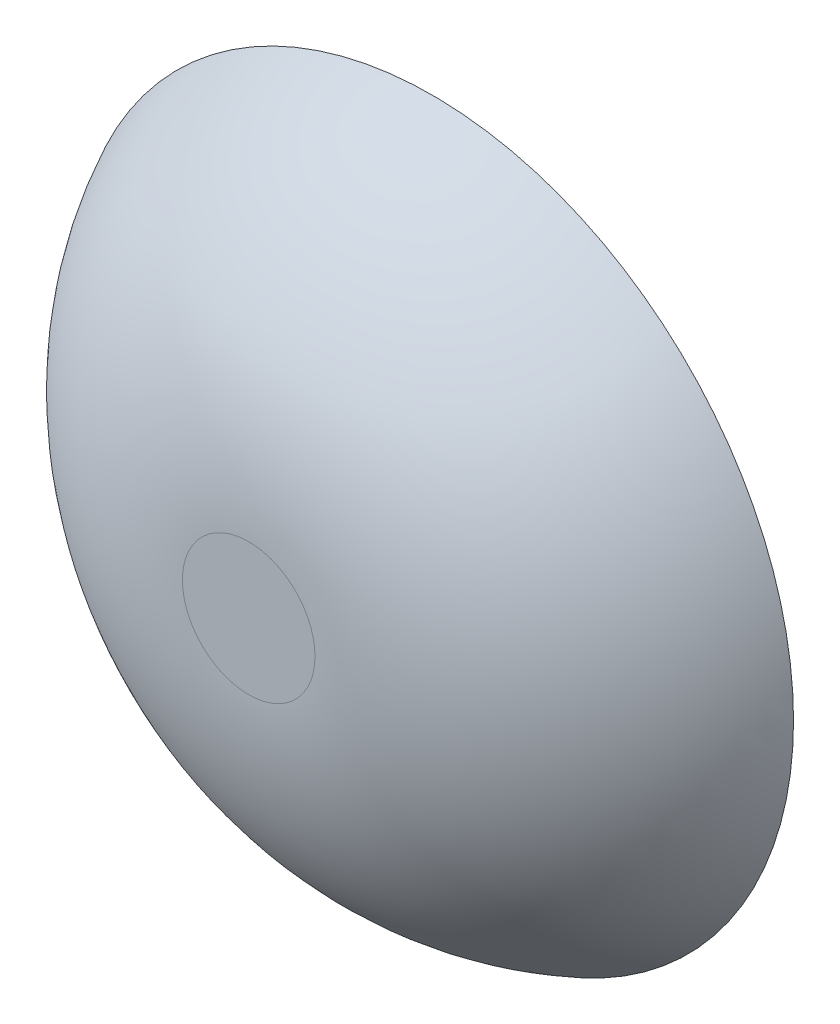
SolidWorks part; units mm, degrees
ref_plane "Plan de face" through (0, 0, 0) normal (0, 0, 1) x (1, 0, 0)
ref_plane "Plan de dessus" through (0, 0, 0) normal (0, 1, 0) x (1, 0, 0)
ref_plane "Plan de droite" through (0, 0, 0) normal (1, 0, 0) x (0, 0, -1)
sketch "Esquisse1" plane through (0, 0, 0) normal (0, 0, 1) x (1, 0, 0)
  circle A0 centre (0, 0) radius 5.5
extrude "Extrusion1" add sketch "Esquisse1" along normal blind 2.8
fillet "Congé1" radius 5 1 edges at (5.5, 0, 2.8)
